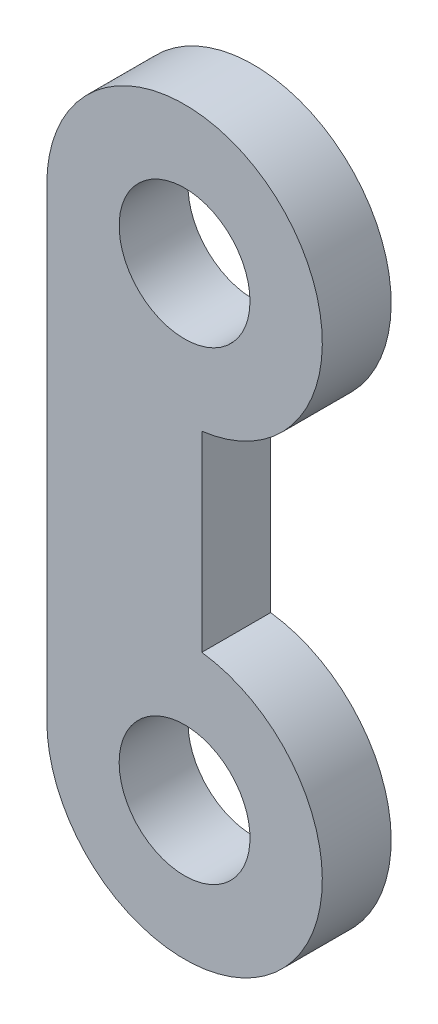
SolidWorks part; units mm, degrees
ref_plane "Płaszczyzna przednia" through (0, 0, 0) normal (0, 0, 1) x (1, 0, 0)
ref_plane "Płaszczyzna górna" through (0, 0, 0) normal (0, 1, 0) x (1, 0, 0)
ref_plane "Płaszczyzna prawa" through (0, 0, 0) normal (1, 0, 0) x (0, 0, -1)
sketch "Sketch1" plane through (0, 0, 0) normal (0, 0, 1) x (1, 0, 0)
  line L0 (-244.6939, 0) -> (11990.0031, 0) construction
  line L1 (-0.1262, 2.7814) -> (-0.1262, -2.7814)
  line L4 (-4.6262, 6.75) -> (-4.6262, -6.75)
  circle A0 centre (-0.6262, 6.75) radius 1.9
  circle A1 centre (-0.6262, -6.75) radius 1.9
  arc A2 (-0.1262, 2.7814) -> (-4.6262, 6.75) centre (-0.6262, 6.75) ccw
  arc A3 (-4.6262, -6.75) -> (-0.1262, -2.7814) centre (-0.6262, -6.75) ccw
  dimension "D1" = 3.8
  dimension "D2" = 4
  dimension "D3" = 0.5
  dimension "D4" = 13.5
extrude "Boss-Extrude1" add sketch "Sketch1" along normal blind 2
